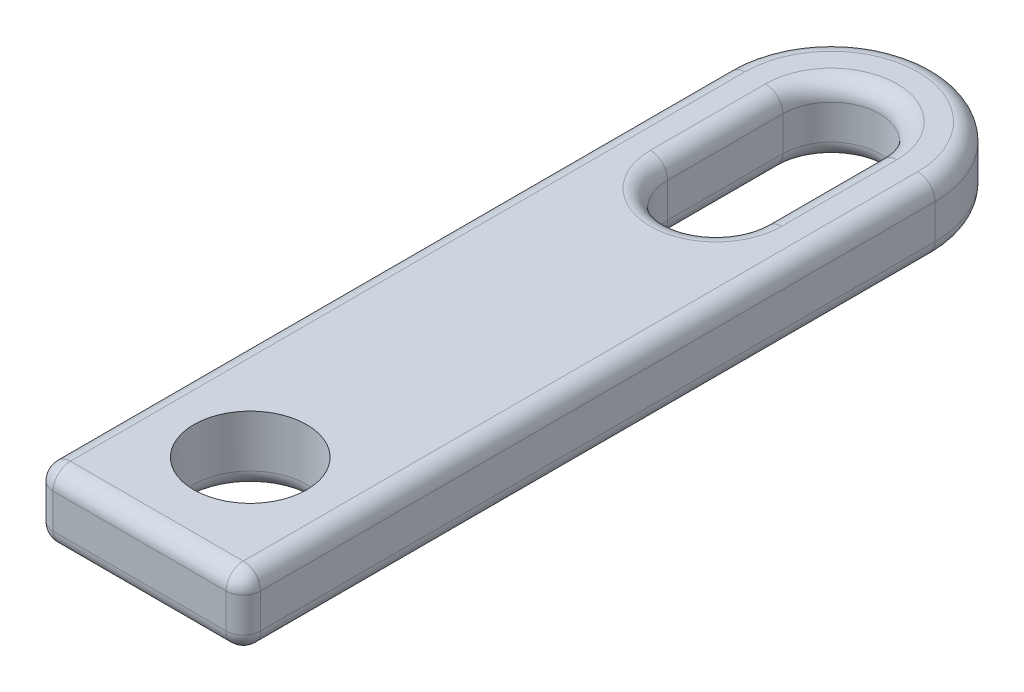
SolidWorks part; units mm, degrees
ref_plane "Front Plane" through (0, 0, 0) normal (0, 0, 1) x (1, 0, 0)
ref_plane "Top Plane" through (0, 0, 0) normal (0, 1, 0) x (1, 0, 0)
ref_plane "Right Plane" through (0, 0, 0) normal (1, 0, 0) x (0, 0, -1)
sketch "Sketch1" plane through (0, 0, 0) normal (0, 1, 0) x (1, 0, 0)
  line L0 (0, -7.4492) -> (0, -12.4492) construction
  line L6 (-4.5, -37.4492) -> (4.5, -37.4492)
  line L8 (2.1, -7.4492) -> (2.1, -12.4492)
  line L9 (-2.1, -7.4492) -> (-2.1, -12.4492)
  line L10 (-4.5, -7.4492) -> (4.5, -7.4492) construction
  line L11 (4.5, -7.4492) -> (4.5, -37.4492)
  line L12 (-4.5, -7.4492) -> (-4.5, -37.4492)
  line L13 (-4.5, -32.6492) -> (4.5, -32.6492) construction
  arc A4 (2.1, -7.4492) -> (-2.1, -7.4492) centre (0, -7.4492) ccw
  circle A5 centre (0, -32.6492) radius 2.45
  arc A6 (-2.1, -12.4492) -> (2.1, -12.4492) centre (0, -12.4492) ccw
  arc A7 (-4.5, -7.4492) -> (4.5, -7.4492) centre (0, -7.4492) cw
  point P3 (0, -9.9492)
  point P15 (0, -32.6492)
  point P17 (0, -7.4492)
  dimension "D5" = 4.8
  dimension "D2" = 2.1
  dimension "D7" = 4.9
  dimension "D3" = 4.5
  dimension "D1" = 5
  dimension "D6" = 25
  dimension "D9" = 9
extrude "Boss-Extrude1" add sketch "Sketch1" along normal blind 3
fillet "Fillet1" radius 0.75 19 edges at (0, 3, 37.4492) (2.1, 0, 9.9492) (0, 0, 14.5492) (-2.1, 0, 9.9492) (0, 0, 5.3492) (0, 0, 37.4492) (0, 3, 2.9492) (0, 0, 2.9492) (0, 3, 5.3492) (2.1, 3, 9.9492) (0, 3, 14.5492) (-2.1, 3, 9.9492) (0, 0, 35.0992) (-4.5, 3, 22.4492) (4.5, 3, 22.4492) (-4.5, 1.5, 37.4492) (4.5, 1.5, 37.4492) (-4.5, 0, 22.4492) (4.5, 0, 22.4492)
